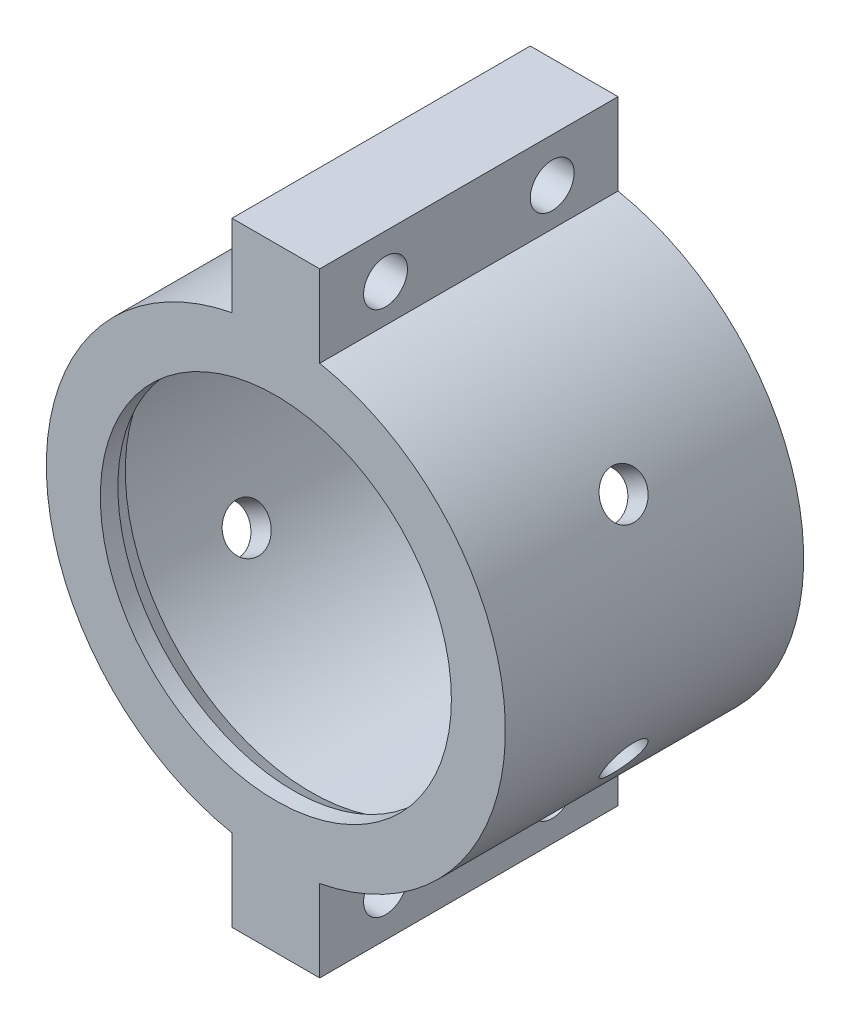
SolidWorks part; units mm, degrees
ref_plane "Front Plane" through (0, 0, 0) normal (0, 0, 1) x (1, 0, 0)
ref_plane "Top Plane" through (0, 0, 0) normal (0, 1, 0) x (1, 0, 0)
ref_plane "Right Plane" through (0, 0, 0) normal (1, 0, 0) x (0, 0, -1)
sketch "Sketch2" plane through (0, 0, 0) normal (0, 1, 0) x (1, 0, 0)
  line L0 (0, 0) -> (25.4085, 0) construction
  line L1 (25.4085, 0) -> (25.4085, 2.54)
  line L2 (25.4085, 2.54) -> (26.875, 5.08)
  line L3 (25.4085, 2.54) -> (25.4085, 5.08) construction
  line L4 (33.225, 5.08) -> (33.225, 0)
  line L5 (33.225, 0) -> (25.4085, 0)
  line L6 (26.875, 5.08) -> (33.225, 5.08)
  line L7 (0, 0) -> (0, 46.1774) construction
  dimension "D2" = 26.875
  dimension "D3" = 5.08
  dimension "D4" = 2.54
  dimension "D5" = 6.35
  dimension "D6" = 30
revolve "Revolve1" add sketch "Sketch2" angle 360 about L7
sketch "Sketch8" plane through (0, 0, 0) normal (0, 1, 0) x (1, 0, 0)
  line L1 (-33.225, 5.08) -> (-33.225, 43.18)
  line L2 (-33.225, 43.18) -> (-29.845, 43.18)
  line L3 (-29.845, 43.18) -> (-29.845, 5.08)
  line L4 (33.225, 5.08) -> (-33.225, 5.08) construction
  line L5 (33.225, 5.08) -> (-33.225, 5.08) construction
  line L6 (-29.845, 5.08) -> (-33.225, 5.08)
  line L7 (0, 0) -> (0, 125.228) construction
  line L8 (-33.225, 0) -> (33.225, 0) construction
  dimension "D3" = 29.845
  dimension "D5" = 38.1
revolve "Revolve2" add sketch "Sketch8" angle 360 about L7
sketch "Sketch19" plane through (0, 0, 0) normal (0, 0, 1) x (1, 0, 0)
  line L0 (-6.35, 32.6125) -> (-6.35, 44.45)
  line L1 (6.35, -44.45) -> (-6.35, -44.45)
  line L2 (6.35, -44.45) -> (6.35, -32.6125)
  line L3 (6.35, 44.45) -> (-6.35, 44.45)
  line L4 (-6.35, -44.45) -> (-6.35, -32.6125)
  line L5 (6.35, -44.45) -> (-6.35, 44.45) construction
  line L6 (6.35, 44.45) -> (-6.35, -44.45) construction
  line L7 (6.35, 32.6125) -> (6.35, 44.45)
  circle A0 centre (0, 0) radius 33.225 construction
  arc A1 (-6.35, -32.6125) -> (6.35, -32.6125) centre (0, 0) ccw
  arc A2 (6.35, 32.6125) -> (-6.35, 32.6125) centre (0, 0) ccw
  dimension "D1" = 12.7
  dimension "D2" = 88.9
extrude "Boss-Extrude10" add sketch "Sketch19" against normal up to surface (43.18 mm away) up to face at (33.225, 0, -43.18)
sketch "Sketch18" plane through (0, 0, 0) normal (1, 0, 0) x (0, 0, -1)
  line L3 (43.18, 44.45) -> (0, 44.45) construction
  line L4 (0, -44.45) -> (0, -32.6125) construction
  line L5 (43.18, -32.6125) -> (43.18, -44.45) construction
  line L6 (43.18, -44.45) -> (0, -44.45) construction
  circle A0 centre (9.525, 38.1) radius 3.175
  circle A1 centre (33.655, 38.1) radius 3.175
  circle A2 centre (9.525, -38.1) radius 3.175
  circle A3 centre (33.655, -38.1) radius 3.175
  dimension "D1" = 6.35
  dimension "D2" = 6.35
  dimension "D3" = 9.525
  dimension "D4" = 9.525
  dimension "D5" = 6.35
extrude "Cut-Extrude7" cut sketch "Sketch18" against normal through all both and the other way through all
sketch "Sketch21" plane through (0, 0, 0) normal (0, 0, 1) x (1, 0, 0)
  line L0 (0, 0) -> (0, 17.0984) construction
  line L1 (0, 0) -> (14.4923, 0) construction
  line L2 (0, 0) -> (14.7479, 8.5147) construction
  line L3 (-30.6026, 53.0053) -> (0, 0) construction
  line L4 (0, 0) -> (37.5938, 65.1143) construction
  dimension "D1" = 30
  dimension "D2" = 30
ref_axis "Axis4" through (0, 0, 3.175) along (0, 0, -1)
ref_plane "Plane1" through (0, 0, 0) normal (-0.866, -0.5, 0) x (-0.5, 0.866, 0)
sketch "Sketch23" plane through (0, 0, 0) normal (-0.866, -0.5, 0) x (-0.5, 0.866, 0)
  line L0 (0, -3.175) -> (0, 66.675) construction
  line L1 (0, 43.18) -> (0, 0) construction
  line L2 (33.225, 43.18) -> (-25.0683, 43.18) construction
  line L3 (-100000, 0) -> (100037.5938, 0) construction
  circle A0 centre (0, 21.59) radius 3.175
  point P13 (0, 21.59)
  dimension "D1" = 6.35
extrude "Cut-Extrude9" cut sketch "Sketch23" against normal through all both and the other way through all
mirror "Mirror3" about plane through (0, 0, 0) normal (0, 1, 0) of "Cut-Extrude9"
